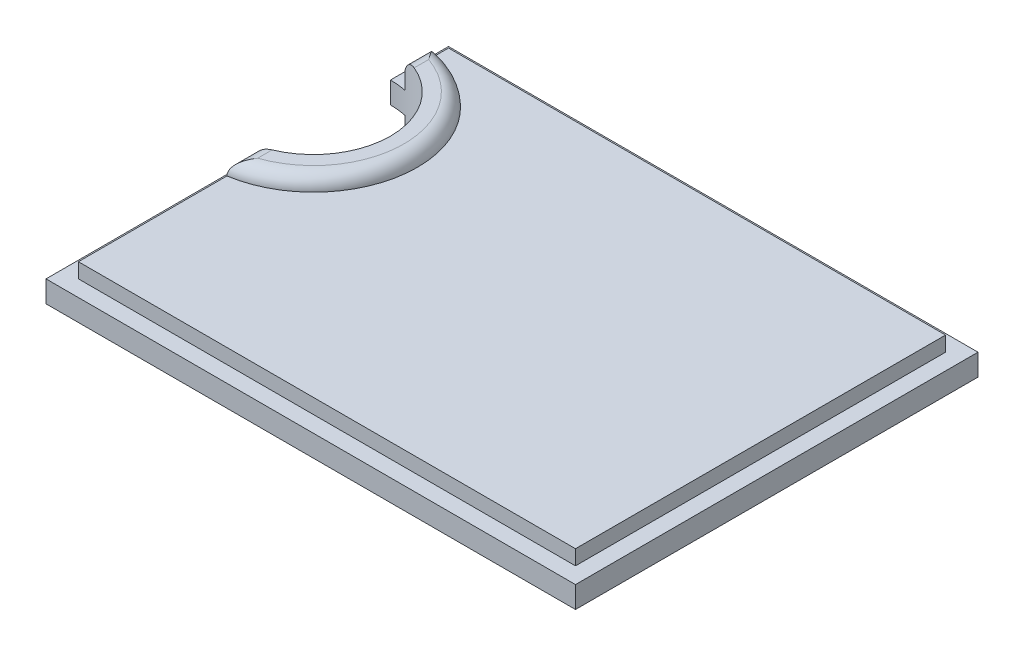
SolidWorks part; units mm, degrees
ref_plane "Front Plane" through (0, 0, 0) normal (0, 0, 1) x (1, 0, 0)
ref_plane "Top Plane" through (0, 0, 0) normal (0, 1, 0) x (1, 0, 0)
ref_plane "Right Plane" through (0, 0, 0) normal (1, 0, 0) x (0, 0, -1)
sketch "Sketch1" plane through (0, 0, 0) normal (0, 1, 0) x (1, 0, 0)
  line L0 (-19.6, 14.9) -> (-19.6, -14.9)
  line L1 (-19.6, -14.9) -> (19.6, -14.9)
  line L2 (19.6, -14.9) -> (19.6, 14.9)
  line L3 (19.6, 14.9) -> (-19.6, 14.9)
  line L4 (18.4, 13.7) -> (-18.4, 13.7)
  line L5 (-18.4, 13.7) -> (-18.4, -13.7)
  line L6 (-18.4, -13.7) -> (18.4, -13.7)
  line L7 (18.4, -13.7) -> (18.4, 13.7)
  line L8 (-18.4, 13.7) -> (0, 0) construction
  line L9 (0, 0) -> (18.4, -13.7) construction
  line L10 (0, 0) -> (18.4, 13.7) construction
  line L11 (0, 0) -> (-18.4, -13.7) construction
  arc A0 (-19.6, 10.6) -> (-19.6, -0.8) centre (-19.6, 4.9) cw
  arc A1 (-19.6, 12.6) -> (-19.6, -2.8) centre (-19.6, 4.9) cw
  point P13 (0, 0)
  point P18 (0, 0)
  dimension "D4" = 5.7
  dimension "D6" = 2
  dimension "D1" = 29.8
  dimension "D2" = 39.2
  dimension "D5" = 10
  dimension "D3" = 1.2
extrude "Boss-Extrude1" add sketch "Sketch1" along normal blind 0.9 contours A1 L5 A0 | L5 A1 L6 L7 L4 region at (-12.0654, 0, -4.9) region at (1.2546, 0, 0.3922)
extrude "Boss-Extrude2" add sketch "Sketch1<5>" along normal blind 1.6 from surface contours L5 A1 L6 L7 L4 | A1 L5 A0 | A1 L0 A0 L5 | L0 A1 L5 L4 L7 L6 L1 L2 L3 | A1 L5 A0 L0 region at (0, 0, -14.4076) region at (-18.9983, 0, -11.563) region at (-12.0654, 0, -4.9) region at (1.2546, 0, 0.3922) region at (-18.9983, 0, 1.763) starting at face at (-5.3833, 0.9, -1.6333)
sketch "Sketch1<5>" plane through (0, 0, 0) normal (0, 1, 0) x (1, 0, 0) same geometry as "Sketch1"
extrude "Boss-Extrude3" add sketch "Sketch1<6>" along normal blind 1.1 from surface contours L5 A1 L6 L7 L4 | A1 L5 A0 region at (-12.0654, 0, -4.9) region at (1.2546, 0, 0.3922) starting at face at (-5.5833, 2.5, -1.6333)
sketch "Sketch1<6>" plane through (0, 0, 0) normal (0, 1, 0) x (1, 0, 0) same geometry as "Sketch1"
extrude "Boss-Extrude4" add sketch "Sketch1<8>" along normal blind 1 from surface contours A1 L5 A0 region at (-12.0654, 0, -4.9) starting at face at (-5.3833, 3.6, -1.6333)
sketch "Sketch1<8>" plane through (0, 0, 0) normal (0, 1, 0) x (1, 0, 0) same geometry as "Sketch1"
fillet "Fillet1" radius 1 3 edges at (-11.9, 4.6, -4.9) (-18.4, 4.6, 1.6891) (-18.4, 4.6, -11.4891)
